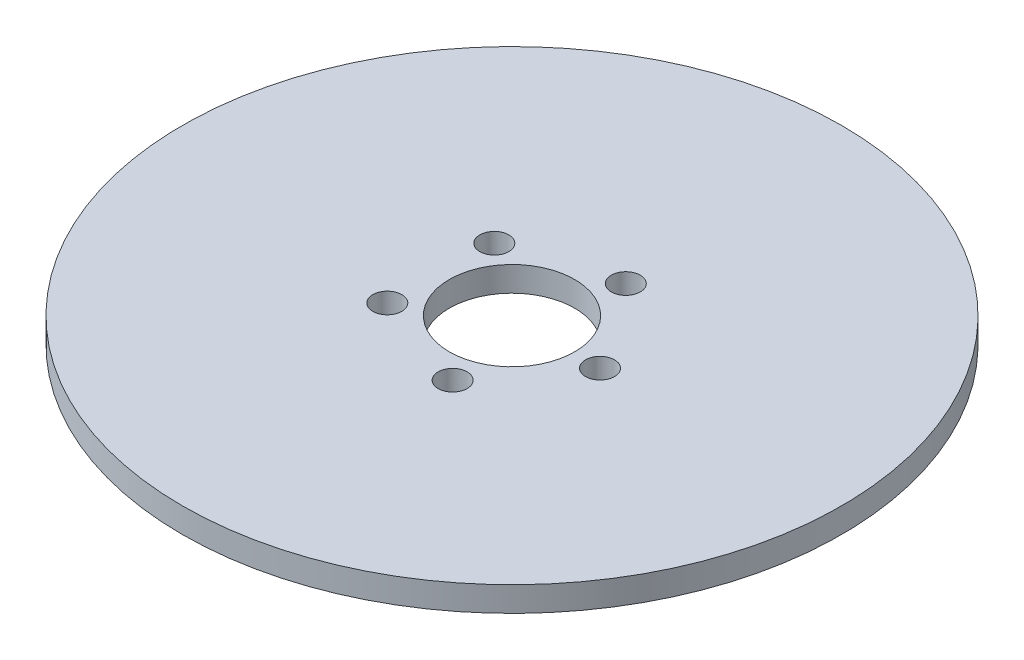
SolidWorks part; units mm, degrees
material "6061 Alloy"
ref_plane "Front Plane" through (0, 0, 0) normal (0, 0, 1) x (1, 0, 0)
ref_plane "Top Plane" through (0, 0, 0) normal (0, 1, 0) x (1, 0, 0)
ref_plane "Right Plane" through (0, 0, 0) normal (1, 0, 0) x (0, 0, -1)
sketch "Sketch1" plane through (0, 1054.464, 0) normal (0, 1, 0) x (-1, 0, 0)
  circle A0 centre (1.2041, -633.1149) radius 42.0697
  circle A3 centre (10.3365, -639.9883) radius 1.8542 construction
  circle A4 centre (-2.5108, -643.9243) radius 1.8542 construction
  circle A5 centre (-10.2243, -632.9221) radius 1.8542 construction
  circle A6 centre (10.5632, -626.5534) radius 1.8542 construction
  circle A7 centre (-2.1441, -622.1863) radius 1.8542 construction
  circle A8 centre (1.2041, -633.1149) radius 8.001
  circle A9 centre (10.3365, -639.9883) radius 1.8542
  circle A10 centre (-2.5108, -643.9243) radius 1.8542
  circle A11 centre (-10.2243, -632.9221) radius 1.8542
  circle A12 centre (10.5632, -626.5534) radius 1.8542
  circle A13 centre (-2.1441, -622.1863) radius 1.8542
  dimension "D1" = 16.002
extrude "Boss-Extrude1" add sketch "Sketch1" against normal blind 3.175
